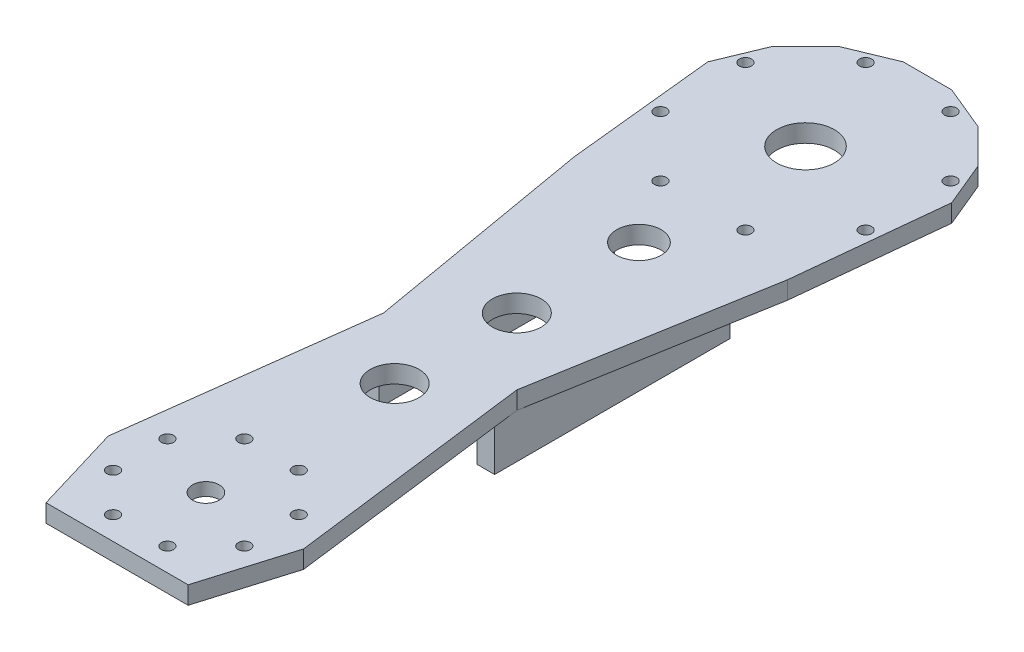
SolidWorks part; units mm, degrees
ref_plane "Front Plane" through (0, 0, 0) normal (0, 0, 1) x (1, 0, 0)
ref_plane "Top Plane" through (0, 0, 0) normal (0, 1, 0) x (1, 0, 0)
ref_plane "Right Plane" through (0, 0, 0) normal (1, 0, 0) x (0, 0, -1)
ref_plane "PL_Thigh_Plate_base" through (0, 36, 0) normal (0, 1, 0) x (1, 0, 0)
sketch "SK_Thigh_Plate" plane through (0, 36, 0) normal (0, 1, 0) x (1, 0, 0)
  line L0 (-32, -40) -> (32, -40)
  line L1 (32, -40) -> (44, 0)
  line L2 (44, 0) -> (30, 110)
  line L3 (30, 110) -> (48, 214)
  line L4 (48, 214) -> (54.924, 280.9251)
  line L5 (54.924, 280.9251) -> (46.5623, 301.1119)
  line L6 (46.5623, 301.1119) -> (31.1119, 316.5623)
  line L7 (31.1119, 316.5623) -> (10.9251, 324.924)
  line L8 (10.9251, 324.924) -> (-10.9251, 324.924)
  line L9 (-10.9251, 324.924) -> (-31.1119, 316.5623)
  line L10 (-31.1119, 316.5623) -> (-46.5623, 301.1119)
  line L11 (-46.5623, 301.1119) -> (-54.924, 280.9251)
  line L12 (-54.924, 280.9251) -> (-48, 214)
  line L13 (-48, 214) -> (-30, 110)
  line L14 (-30, 110) -> (-44, 0)
  line L15 (-44, 0) -> (-32, -40)
  circle A0 centre (29.5641, 12.2459) radius 2.75
  circle A1 centre (12.2459, 29.5641) radius 2.75
  circle A2 centre (-12.2459, 29.5641) radius 2.75
  circle A3 centre (-29.5641, 12.2459) radius 2.75
  circle A4 centre (-29.5641, -12.2459) radius 2.75
  circle A5 centre (-12.2459, -29.5641) radius 2.75
  circle A6 centre (12.2459, -29.5641) radius 2.75
  circle A7 centre (29.5641, -12.2459) radius 2.75
  circle A8 centre (46.194, 289.1342) radius 2.75
  circle A9 centre (19.1342, 316.194) radius 2.75
  circle A10 centre (-19.1342, 316.194) radius 2.75
  circle A11 centre (-46.194, 289.1342) radius 2.75
  circle A12 centre (-46.194, 250.8658) radius 2.75
  circle A13 centre (-19.1342, 223.806) radius 2.75
  circle A14 centre (19.1342, 223.806) radius 2.75
  circle A15 centre (46.194, 250.8658) radius 2.75
  circle A16 centre (0, 0) radius 6
  circle A17 centre (0, 270) radius 13
  circle A18 centre (0, 85) radius 11
  circle A19 centre (0, 140) radius 11
  circle A20 centre (0, 195) radius 10
  dimension "D31_SK_Thigh_Plate" = 5.5
  dimension "D34_SK_Thigh_Plate" = 5.5
  dimension "D37_SK_Thigh_Plate" = 5.5
  dimension "D40_SK_Thigh_Plate" = 5.5
  dimension "D43_SK_Thigh_Plate" = 5.5
  dimension "D46_SK_Thigh_Plate" = 5.5
  dimension "D49_SK_Thigh_Plate" = 5.5
  dimension "D52_SK_Thigh_Plate" = 5.5
  dimension "D55_SK_Thigh_Plate" = 5.5
  dimension "D58_SK_Thigh_Plate" = 5.5
  dimension "D61_SK_Thigh_Plate" = 5.5
  dimension "D64_SK_Thigh_Plate" = 5.5
  dimension "D67_SK_Thigh_Plate" = 5.5
  dimension "D70_SK_Thigh_Plate" = 5.5
  dimension "D73_SK_Thigh_Plate" = 5.5
  dimension "D76_SK_Thigh_Plate" = 5.5
  dimension "D79_SK_Thigh_Plate" = 12
  dimension "D80_SK_Thigh_Plate" = 26
  dimension "D82_SK_Thigh_Plate" = 22
  dimension "D84_SK_Thigh_Plate" = 22
  dimension "D86_SK_Thigh_Plate" = 20
  dimension "P1" = 32
  dimension "P2" = 40
  dimension "P3" = 32
  dimension "P4" = 40
  dimension "P5" = 44
  dimension "P6" = 30
  dimension "P7" = 110
  dimension "P8" = 48
  dimension "P9" = 214
  dimension "P10" = 54.924
  dimension "P11" = 280.9251
  dimension "P12" = 46.5623
  dimension "P13" = 301.1119
  dimension "P14" = 31.1119
  dimension "P15" = 316.5623
  dimension "P16" = 10.9251
  dimension "P17" = 324.924
  dimension "P18" = 10.9251
  dimension "P19" = 324.924
  dimension "P20" = 31.1119
  dimension "P21" = 316.5623
  dimension "P22" = 46.5623
  dimension "P23" = 301.1119
  dimension "P24" = 54.924
  dimension "P25" = 280.9251
  dimension "P26" = 48
  dimension "P27" = 214
  dimension "P28" = 30
  dimension "P29" = 110
  dimension "P30" = 44
  dimension "P32" = 29.5641
  dimension "P33" = 12.2459
  dimension "P35" = 12.2459
  dimension "P36" = 29.5641
  dimension "P38" = 12.2459
  dimension "P39" = 29.5641
  dimension "P41" = 29.5641
  dimension "P42" = 12.2459
  dimension "P44" = 29.5641
  dimension "P45" = 12.2459
  dimension "P47" = 12.2459
  dimension "P48" = 29.5641
  dimension "P50" = 12.2459
  dimension "P51" = 29.5641
  dimension "P53" = 29.5641
  dimension "P54" = 12.2459
  dimension "P56" = 46.194
  dimension "P57" = 289.1342
  dimension "P59" = 19.1342
  dimension "P60" = 316.194
  dimension "P62" = 19.1342
  dimension "P63" = 316.194
  dimension "P65" = 46.194
  dimension "P66" = 289.1342
  dimension "P68" = 46.194
  dimension "P69" = 250.8658
  dimension "P71" = 19.1342
  dimension "P72" = 223.806
  dimension "P74" = 19.1342
  dimension "P75" = 223.806
  dimension "P77" = 46.194
  dimension "P78" = 250.8658
  dimension "P81" = 270
  dimension "P83" = 85
  dimension "P85" = 140
  dimension "P87" = 195
extrude "Thigh_Plate" add sketch "SK_Thigh_Plate" along normal blind 8
ref_plane "PL_Pitch_Pilot_Recess_base" through (0, 36, 0) normal (0, 1, 0) x (1, 0, 0)
sketch "SK_Pitch_Pilot_Recess" plane through (0, 36, 0) normal (0, 1, 0) x (1, 0, 0)
  circle A0 centre (0, 0) radius 25.15
  dimension "D1_SK_Pitch_Pilot_Recess" = 50.3
extrude "Pitch_Pilot_Recess" cut sketch "SK_Pitch_Pilot_Recess" along normal blind 2.2
ref_plane "PL_Front_Flange_base" through (22, 0, 0) normal (1, 0, 0) x (0, 0, -1)
sketch "SK_Front_Flange" plane through (22, 0, 0) normal (1, 0, 0) x (0, 0, -1)
  line L0 (206, 16) -> (206, 36)
  line L1 (206, 36) -> (100, 36)
  line L2 (100, 36) -> (100, 16)
  line L3 (100, 16) -> (206, 16)
  dimension "P1" = 206
  dimension "P2" = 16
  dimension "P3" = 206
  dimension "P4" = 36
  dimension "P5" = 100
  dimension "P6" = 36
  dimension "P7" = 100
  dimension "P8" = 16
extrude "Front_Flange" add sketch "SK_Front_Flange" along normal blind 8
ref_plane "PL_Back_Flange_base" through (-30, 0, 0) normal (1, 0, 0) x (0, 0, -1)
sketch "SK_Back_Flange" plane through (-30, 0, 0) normal (1, 0, 0) x (0, 0, -1)
  line L0 (206, 16) -> (206, 36)
  line L1 (206, 36) -> (100, 36)
  line L2 (100, 36) -> (100, 16)
  line L3 (100, 16) -> (206, 16)
  dimension "P1" = 206
  dimension "P2" = 16
  dimension "P3" = 206
  dimension "P4" = 36
  dimension "P5" = 100
  dimension "P6" = 36
  dimension "P7" = 100
  dimension "P8" = 16
extrude "Back_Flange" add sketch "SK_Back_Flange" along normal blind 8
ref_axis "AX_PitchY" through (0, 45.4, 0) along (0, -1, 0)
ref_plane "PL_PitchRef" through (0, 0, 0) normal (-0.6428, 0, 0.766) x (0, -1, 0)
equation "\"Thigh_length\" = 270"
equation "\"Thigh_plate_t\" = 8"
equation "\"Flange_end_z\" = -206"
